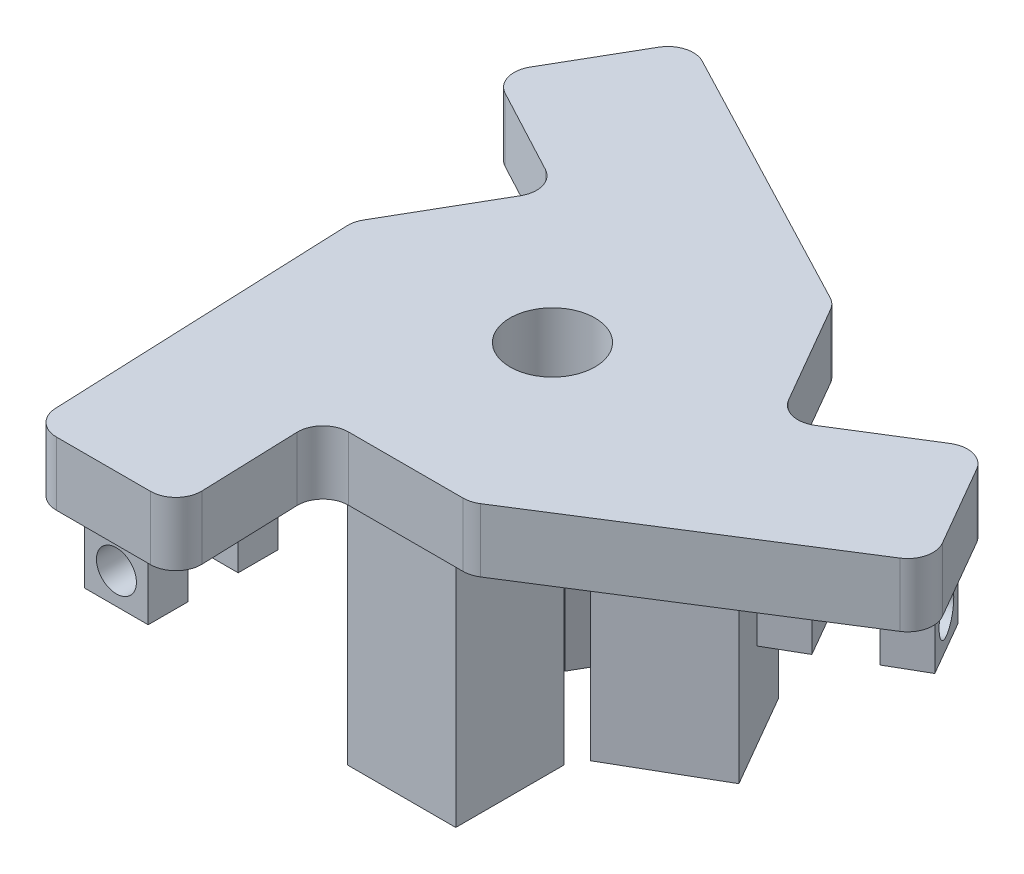
SolidWorks part; units mm, degrees
ref_plane "Front Plane" through (0, 0, 0) normal (0, 0, 1) x (1, 0, 0)
ref_plane "Top Plane" through (0, 0, 0) normal (0, 1, 0) x (1, 0, 0)
ref_plane "Right Plane" through (0, 0, 0) normal (1, 0, 0) x (0, 0, -1)
sketch "Sketch1" plane through (0, 0, 0) normal (0, 1, 0) x (1, 0, 0)
  line L1 (19.05, -32.9956) -> (38.1, 0)
  line L2 (38.1, 0) -> (19.05, 32.9956)
  line L3 (19.05, 32.9956) -> (-19.05, 32.9956)
  line L4 (-19.05, 32.9956) -> (-38.1, 0)
  line L5 (-38.1, 0) -> (-19.05, -32.9956)
  line L6 (-19.05, -32.9956) -> (19.05, -32.9956)
  circle A0 centre (0, 0) radius 32.9956 construction
  dimension "D1" = 38.1
extrude "Boss-Extrude1" add sketch "Sketch1" along normal blind 6.35 contours L4 L5 L6 L1 L2 L3
sketch "Sketch2" plane through (0, 0, 0) normal (0, -1, 0) x (1, 0, 0)
  line L0 (-5.425, 15.1) -> (-5.425, 4.25)
  line L5 (-3.425, 13.1) -> (3.425, 13.1)
  line L6 (-3.425, 13.1) -> (-3.425, 6.25)
  line L7 (-3.425, 6.25) -> (3.425, 6.25)
  line L8 (3.425, 13.1) -> (3.425, 6.25)
  line L9 (-3.425, 13.1) -> (3.425, 6.25) construction
  line L10 (-3.425, 6.25) -> (3.425, 13.1) construction
  line L11 (-5.425, 4.25) -> (-2.067, 4.25)
  line L12 (5.425, 15.1) -> (5.425, 4.25)
  line L13 (-5.425, 15.1) -> (5.425, 15.1)
  line L14 (2.067, 4.25) -> (5.425, 4.25)
  line L15 (-5.425, 4.25) -> (5.425, 4.25) construction
  line L16 (13.0574, -3.5839) -> (7.1252, -0.1589)
  line L17 (13.0574, -3.5839) -> (9.6324, -9.5161)
  line L18 (9.6324, -9.5161) -> (3.7002, -6.0911)
  line L19 (7.1252, -0.1589) -> (3.7002, -6.0911)
  line L20 (2.6471, -3.9151) -> (0.9681, -6.8232)
  line L21 (10.3645, -12.2482) -> (0.9681, -6.8232)
  line L22 (15.7895, -2.8518) -> (10.3645, -12.2482)
  line L23 (15.7895, -2.8518) -> (6.3931, 2.5732)
  line L24 (6.3931, 2.5732) -> (4.7141, -0.3349)
  line L25 (-9.6324, -9.5161) -> (-3.7002, -6.0911)
  line L26 (-9.6324, -9.5161) -> (-13.0574, -3.5839)
  line L27 (-13.0574, -3.5839) -> (-7.1252, -0.1589)
  line L28 (-3.7002, -6.0911) -> (-7.1252, -0.1589)
  line L29 (-4.7141, -0.3349) -> (-6.3931, 2.5732)
  line L30 (-15.7895, -2.8518) -> (-6.3931, 2.5732)
  line L31 (-10.3645, -12.2482) -> (-15.7895, -2.8518)
  line L32 (-10.3645, -12.2482) -> (-0.9681, -6.8232)
  line L33 (-0.9681, -6.8232) -> (-2.6471, -3.9151)
  circle A0 centre (0, 0) radius 4.726 construction
  arc A2 (-2.067, 4.25) -> (2.067, 4.25) centre (0, 0) cw
  arc A3 (4.7141, -0.3349) -> (2.6471, -3.9151) centre (0, 0) cw
  arc A4 (-2.6471, -3.9151) -> (-4.7141, -0.3349) centre (0, 0) cw
  point P3 (0, 9.675)
  point P37 (0, 0)
  dimension "D1" = 9.675
  dimension "D3" = 1.524
  dimension "D4" = 2
  dimension "D2" = 6.85
  dimension "D5" = 3
sketch "Sketch6" plane through (0, 6.35, 0) normal (0, 1, 0) x (1, 0, 0)
  circle A0 centre (0, 0) radius 4.25
  dimension "D1" = 8.5
extrude "Cut-Extrude1" cut sketch "Sketch6" against normal through all
extrude "Boss-Extrude2" add sketch "Sketch2" along normal blind 25.4
sketch "Sketch7" plane through (0, 0, 0) normal (0, -1, 0) x (1, 0, 0)
  line L0 (-14.8153, 22.9723) -> (-8.4653, 22.9723)
  line L1 (-8.4653, 22.9723) -> (-8.4653, 18.9723)
  line L2 (-8.4653, 18.9723) -> (-14.8153, 18.9723)
  line L3 (-14.8153, 18.9723) -> (-14.8153, 22.9723)
  line L4 (-19.05, -32.9956) -> (-38.1, 0) construction
  line L5 (-19.05, 32.9956) -> (19.05, 32.9956) construction
  line L6 (38.1, 0) -> (19.05, -32.9956) construction
  line L7 (-14.8153, 27.9723) -> (-14.8153, 31.9723)
  line L8 (-14.8153, 31.9723) -> (-8.4653, 31.9723)
  line L9 (-8.4653, 31.9723) -> (-8.4653, 27.9723)
  line L10 (-8.4653, 27.9723) -> (-14.8153, 27.9723)
  line L11 (-5.425, 15.1) -> (-5.425, 4.25) construction
  line L12 (27.2966, 1.354) -> (24.1216, -4.1453)
  line L13 (24.1216, -4.1453) -> (20.6575, -2.1453)
  line L14 (20.6575, -2.1453) -> (23.8325, 3.354)
  line L15 (23.8325, 3.354) -> (27.2966, 1.354)
  line L16 (31.6268, -1.146) -> (35.0909, -3.146)
  line L17 (35.0909, -3.146) -> (31.9159, -8.6453)
  line L18 (31.9159, -8.6453) -> (28.4518, -6.6453)
  line L19 (28.4518, -6.6453) -> (31.6268, -1.146)
  line L20 (-12.4813, -24.3068) -> (-15.6563, -18.8076)
  line L21 (-15.6563, -18.8076) -> (-12.1922, -16.8076)
  line L22 (-12.1922, -16.8076) -> (-9.0172, -22.3068)
  line L23 (-9.0172, -22.3068) -> (-12.4813, -24.3068)
  line L24 (-16.8115, -26.8068) -> (-20.2756, -28.8068)
  line L25 (-20.2756, -28.8068) -> (-23.4506, -23.3076)
  line L26 (-23.4506, -23.3076) -> (-19.9865, -21.3076)
  line L27 (-19.9865, -21.3076) -> (-16.8115, -26.8068)
  point P13 (-11.6403, 18.9723)
  dimension "D1" = 22.9723
  dimension "D2" = 4
  dimension "D4" = 5
  dimension "D5" = 6.2153
  dimension "D6" = 6.35
  dimension "D8" = 1.033
  dimension "D9" = 1.033
  dimension "D3" = 2
  dimension "D7" = 3
extrude "Boss-Extrude3" add sketch "Sketch7" along normal blind 6.35
sketch "Sketch9" plane through (0, 0, 31.9723) normal (0, 0, 1) x (1, 0, 0)
  line L0 (-8.4653, -6.35) -> (-14.8153, -6.35) construction
  line L1 (-19.05, 0) -> (19.05, 0) construction
  circle A0 centre (-11.6403, -3.2626) radius 2
  point P4 (-11.6403, -6.35)
  dimension "D1" = 4
  dimension "D2" = 3.2626
extrude "Cut-Extrude2" cut sketch "Sketch9" against normal blind 6.54
pattern_circular "CirPattern1" count 3 over 360 about axis through (0, 0, 0) along (0, 1, 0) of "Cut-Extrude2" reverse direction yes
sketch "Sketch10" plane through (0, 0, 22.9723) normal (0, 0, 1) x (1, 0, 0)
  circle A0 centre (-11.6403, -3.2626) radius 1.7145
  dimension "D1" = 3.429
extrude "Cut-Extrude3" cut sketch "Sketch10" against normal blind 2
pattern_circular "CirPattern2" count 3 over 360 about axis through (0, 0, 0) along (0, 1, 0) of "Cut-Extrude3"
sketch "Sketch11" plane through (0, 0, 0) normal (0, -1, 0) x (1, 0, 0)
  line L0 (-38.1, 0) -> (-19.05, 32.9956)
  line L1 (-19.05, -32.9956) -> (-38.1, 0) construction
  line L2 (-38.1, 0) -> (-19.05, 32.9956) construction
  line L5 (-20.4169, -0.5354) -> (-12.9994, -13.3828)
  line L6 (-12.9994, -13.3828) -> (-26.2859, -20.4626)
  line L7 (-26.2859, -20.4626) -> (-38.1, 0)
  line L21 (-19.05, 32.9956) -> (-20.4169, -0.5354)
  line L22 (19.05, 32.9956) -> (38.1, 0)
  line L23 (9.7447, 17.9492) -> (-5.0901, 17.9492)
  line L24 (-5.0901, 17.9492) -> (-4.5782, 32.9956)
  line L25 (-4.5782, 32.9956) -> (19.05, 32.9956)
  line L26 (38.1, 0) -> (9.7447, 17.9492)
  line L27 (19.05, -32.9956) -> (-19.05, -32.9956)
  line L28 (10.6721, -17.4138) -> (18.0896, -4.5665)
  line L29 (18.0896, -4.5665) -> (30.8641, -12.533)
  line L30 (30.8641, -12.533) -> (19.05, -32.9956)
  line L31 (-19.05, -32.9956) -> (10.6721, -17.4138)
  point P21 (0, 0)
  dimension "D1" = 3
extrude "Cut-Extrude4" cut sketch "Sketch11" against normal up to surface (6.35 mm away) up to face at (0, 6.35, 4.25)
fillet "Fillet1" radius 2.54 12 edges at (18.0896, 3.175, -4.5665) (-12.9994, 3.175, -13.3828) (-5.0901, 3.175, 17.9492) (-19.05, 3.175, 32.9956) (-4.5782, 3.175, 32.9956) (-26.2859, 3.175, -20.4626) (-19.05, 3.175, -32.9956) (30.8641, 3.175, -12.533) (38.1, 3.175, 0) (9.7447, 3.175, 17.9492) (-20.4169, 3.175, -0.5354) (10.6721, 3.175, -17.4138)
